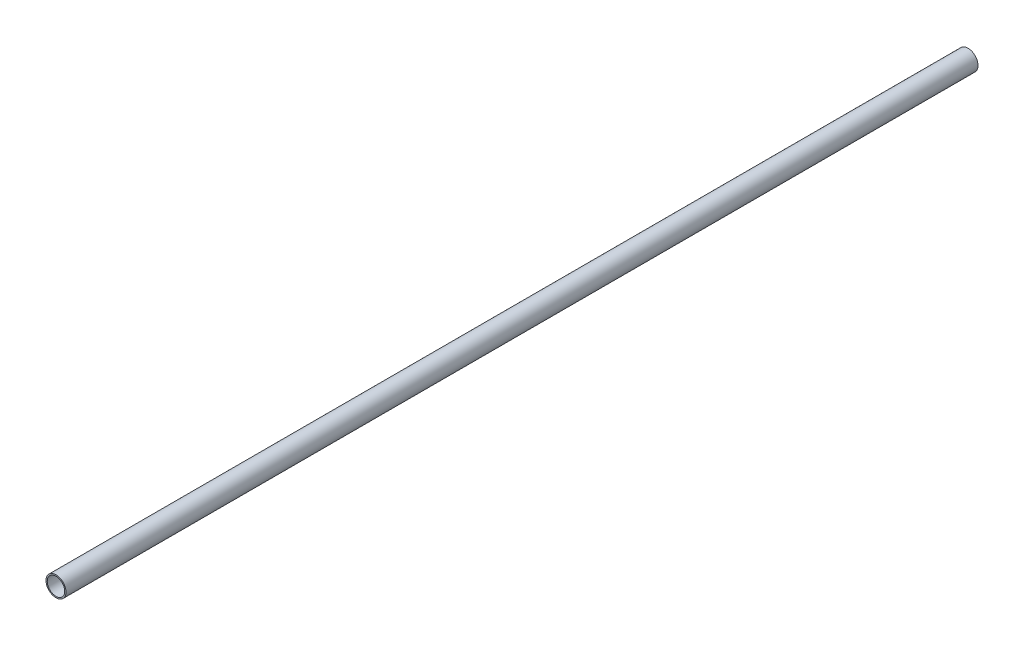
SolidWorks part; units mm, degrees
material "CarbonFiber"
ref_plane "Спереди" through (0, 0, 0) normal (0, 0, 1) x (1, 0, 0)
ref_plane "Сверху" through (0, 0, 0) normal (0, 1, 0) x (1, 0, 0)
ref_plane "Справа" through (0, 0, 0) normal (1, 0, 0) x (0, 0, -1)
sketch "Эскиз1" plane through (0, 0, 0) normal (0, 0, 1) x (1, 0, 0)
  circle A1 centre (0, 0) radius 8
  circle A2 centre (0, 0) radius 7
  dimension "D1" = 16
  dimension "D2" = 1
extrude "Бобышка-Вытянуть1" add sketch "Эскиз1" along normal mid plane 730
equation "\"DTailTube\"= 16мм'Диаметр трубки хвостового оперения"
equation "\"FusLenght\"= 700мм"
equation "\"DMotor\"= 35.2мм"
equation "\"MotorArm\"= 320мм"
equation "\"DFus\"= 150мм"
equation "\"DFusTube\"= 30мм'Диаметр трубки внутри фюзеляжа"
equation "\"FusTubeHeight\"= 40мм"
equation "\"FusCentralPartLenght\"= 410мм"
equation "\"FusNoseLenght\"= 150мм"
equation "\"WingOffset\"= 1мм'Расстояние от внутренней поверхности фюзеляжа до профиля крыла по вертикали"
equation "\"EllipseRatio\"= 0.95'Центральная часть фюзеляжа - эллипс. Этот параметр - отношение длин осей эллипса"
equation "\"FrameOffset\"= 0.6мм"
equation "\"DThreadedInsert\"= 3.6мм'Внешний диамер резьбовых втулок"
equation "\"CenterSectionLenght\"= 140мм'Длина центроплана"
equation "\"b\"= 1700мм'Размах"
equation "\"cwr\"= 236мм'Корневая хорда крыла"
equation "\"TR\"= 0.75'Сужение крыла"
equation "\"cwt\"= \"TR\" * \"cwr\"'Концевая хорда крыла"
equation "\"DWingMainSpar\"= 16мм'Диаметр главного лонжерона крыла"
equation "\"DWingSecondSpar\"= 8мм'Диаметр второго лонжерона крыла"
equation "\"WingSparsDistance\"= 80мм'Расстояния между отверстиями по лонжерон крыла"
equation "\"c\"= 210мм'САХ крыла"
equation "\"FusTubeLenght\"= \"FusLenght\"-50мм'Длина трубки фюзеляжа"
equation "\"bt\"=291мм'Высота лопатки хвоста"
equation "\"D1@Эскиз1\"=\"DTailTube\""
equation "\"TailTubeLenght\"=730мм'Длина хвостовой балки"
equation "\"D1@Бобышка-Вытянуть1\"=\"TailTubeLenght\""
equation "\"ct\"=182мм'Корневая хорда хвоста"
equation "\"lambda_t\"=0.3'Доля хвоста, занатая рулем высоты"
equation "\"DStringer\"=6мм'Диаметр стрингеров"
equation "\"TailConnectorBaseLenght\"=20мм'Высота основания конектора хвоста"
equation "\"CargoHolderHoleDistance\"=30мм'Расстояние между крепежными отверстиями для держателя груза"
equation "\"FuselageThickness\"=1.2мм'Толщина фюзеляжа"
equation "\"DTailSpar\"=6мм'Диаметр лонжерона хвостового оперения"
equation "\"TailSparDistance\"=40мм'Расстояние между лонжеронами хвостового оперения"
equation "\"CrossSectionWidth\"=15мм'Ширина кольцевой части шпангоута"
